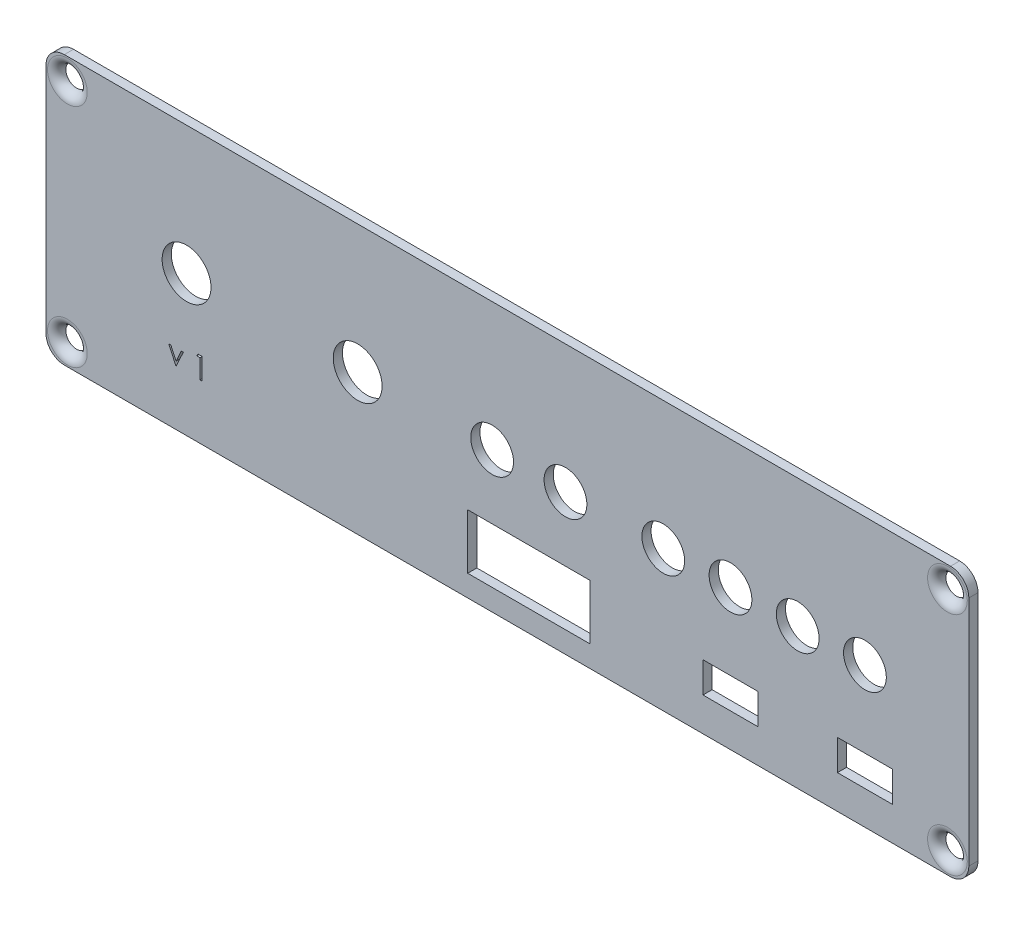
SolidWorks part; units mm, degrees
ref_plane "Front Plane" through (0, 0, 0) normal (0, 0, 1) x (1, 0, 0)
ref_plane "Top Plane" through (0, 0, 0) normal (0, 1, 0) x (1, 0, 0)
ref_plane "Right Plane" through (0, 0, 0) normal (1, 0, 0) x (0, 0, -1)
sketch "Sketch1" plane through (0, 0, 0) normal (0, 0, 1) x (1, 0, 0)
  line L1 (75.5, -22) -> (-75.5, -22)
  line L2 (75.5, -22) -> (75.5, 22)
  line L3 (75.5, 22) -> (-75.5, 22)
  line L4 (-75.5, -22) -> (-75.5, 22)
  line L5 (75.5, -22) -> (-75.5, 22) construction
  line L6 (75.5, 22) -> (-75.5, -22) construction
  point P0 (0, 0)
  dimension "D1" = 151
  dimension "D2" = 44
extrude "main_body" add sketch "Sketch1" along normal blind 1.5
fillet "body_corners" radius 3 4 edges at (-75.5, -22, 0.75) (75.5, -22, 0.75) (75.5, 22, 0.75) (-75.5, 22, 0.75)
sketch "Sketch2" plane through (0, 0, 1.5) normal (0, 0, 1) x (1, 0, 0)
  line L0 (-75.5, 18.5) -> (75.5, 18.5) construction
  line L1 (-75.5, 19) -> (-75.5, -19) construction
  line L2 (75.5, -19) -> (75.5, 19) construction
  line L3 (-72, 22) -> (-72, -22) construction
  line L4 (-75.5, -18.5) -> (75.5, -18.5) construction
  line L8 (72.5, 22) -> (-72.5, 22) construction
  line L9 (72, 22) -> (72, -22) construction
  line L10 (-72.5, -22) -> (72.5, -22) construction
  circle A1 centre (-72, -18.5) radius 1.75
  circle A2 centre (72, 18.5) radius 1.75
  circle A3 centre (72, -18.5) radius 1.75
  circle A4 centre (-72, 18.5) radius 1.75
  dimension "D5" = 3.5
  dimension "D6" = 3.5
  dimension "D7" = 3.5
  dimension "D8" = 3.5
  dimension "D1" = 3.5
  dimension "D2" = 3.5
  dimension "D3" = 3.5
  dimension "D4" = 3.5
extrude "mounting_holes" cut sketch "Sketch2" against normal blind 1.5
fillet "bolt_heads" radius 1.5 4 edges at (-70.25, 18.5, 1.5) (-70.25, -18.5, 1.5) (73.75, -18.5, 1.5) (73.75, 18.5, 1.5)
sketch "Sketch3" plane through (0, 0, 1.5) normal (0, 0, 1) x (1, 0, 0)
  line L0 (-75.5, 1) -> (75.5, 1) construction
  line L1 (-75.5, 19) -> (-75.5, -19) construction
  line L2 (75.5, -19) -> (75.5, 19) construction
  line L3 (72.5, 22) -> (-72.5, 22) construction
  line L4 (-72.5, -22) -> (72.5, -22) construction
  line L5 (75.5, -14) -> (-75.5, -14) construction
  line L6 (58.5, 22) -> (58.5, -22) construction
  line L7 (9.5, 22) -> (9.5, -22) construction
  line L9 (47.5, -22) -> (47.5, 22) construction
  line L12 (36.5, 22) -> (36.5, -22) construction
  line L15 (25.5, -22) -> (25.5, 22) construction
  line L21 (3.5, 22) -> (3.5, -22) construction
  line L22 (-2.5, 22) -> (-2.5, -22) construction
  line L24 (-24.5, 22) -> (-24.5, -22) construction
  line L26 (-52.5, 22) -> (-52.5, -22) construction
  line L29 (63, -16.5) -> (54, -16.5)
  line L30 (63, -16.5) -> (63, -11.5)
  line L37 (63, -11.5) -> (54, -11.5)
  line L38 (54, -16.5) -> (54, -11.5)
  line L39 (63, -16.5) -> (54, -11.5) construction
  line L40 (63, -11.5) -> (54, -16.5) construction
  line L45 (41, -16.5) -> (32, -16.5)
  line L46 (41, -16.5) -> (41, -11.5)
  line L50 (13.5, -18.5) -> (-6.5, -18.5)
  line L51 (41, -11.5) -> (32, -11.5)
  line L52 (32, -16.5) -> (32, -11.5)
  line L53 (41, -16.5) -> (32, -11.5) construction
  line L54 (41, -11.5) -> (32, -16.5) construction
  line L55 (13.5, -18.5) -> (13.5, -9.5)
  line L56 (13.5, -9.5) -> (-6.5, -9.5)
  line L57 (-6.5, -18.5) -> (-6.5, -9.5)
  line L58 (13.5, -18.5) -> (-6.5, -9.5) construction
  line L59 (13.5, -9.5) -> (-6.5, -18.5) construction
  circle A1 centre (47.5, 1) radius 3.5
  circle A2 centre (36.5, 1) radius 3.5
  circle A3 centre (25.5, 1) radius 3.5
  circle A6 centre (58.5, 1) radius 3.5
  circle A9 centre (9.5, 1) radius 3.5
  circle A13 centre (-2.5, 1) radius 3.5
  circle A14 centre (-24.5, 1) radius 4
  circle A15 centre (-52.5, 1) radius 4
  point P28 (58.5, -14)
  point P49 (36.5, -14)
  point P56 (3.5, -14)
  dimension "D7" = 7
  dimension "D8" = 5
  dimension "D9" = 7
  dimension "D10" = 9
  dimension "D11" = 7
  dimension "D12" = 7
  dimension "D13" = 66
  dimension "D14" = 78
  dimension "D15" = 100
  dimension "D21" = 7
  dimension "D22" = 7
  dimension "D23" = 8
  dimension "D24" = 8
  dimension "D1" = 21
  dimension "D2" = 8
  dimension "D3" = 17
  dimension "D4" = 28
  dimension "D5" = 39
  dimension "D6" = 50
  dimension "D16" = 128
  dimension "D17" = 72
  dimension "D18" = 9
  dimension "D19" = 5
  dimension "D20" = 9
  dimension "D25" = 20
extrude "connectors" cut sketch "Sketch3" against normal blind 1.5
sketch "Sketch4" plane through (0, 0, 1.5) normal (0, 0, 1) x (1, 0, 0)
  line L0 (-75.5, 19) -> (-75.5, -19) construction
  line L1 (-72.5, -22) -> (72.5, -22) construction
  text T0 "v 1"
  dimension "D1" = 20
  dimension "D2" = 9
extrude "version" cut sketch "Sketch4" against normal blind 1
